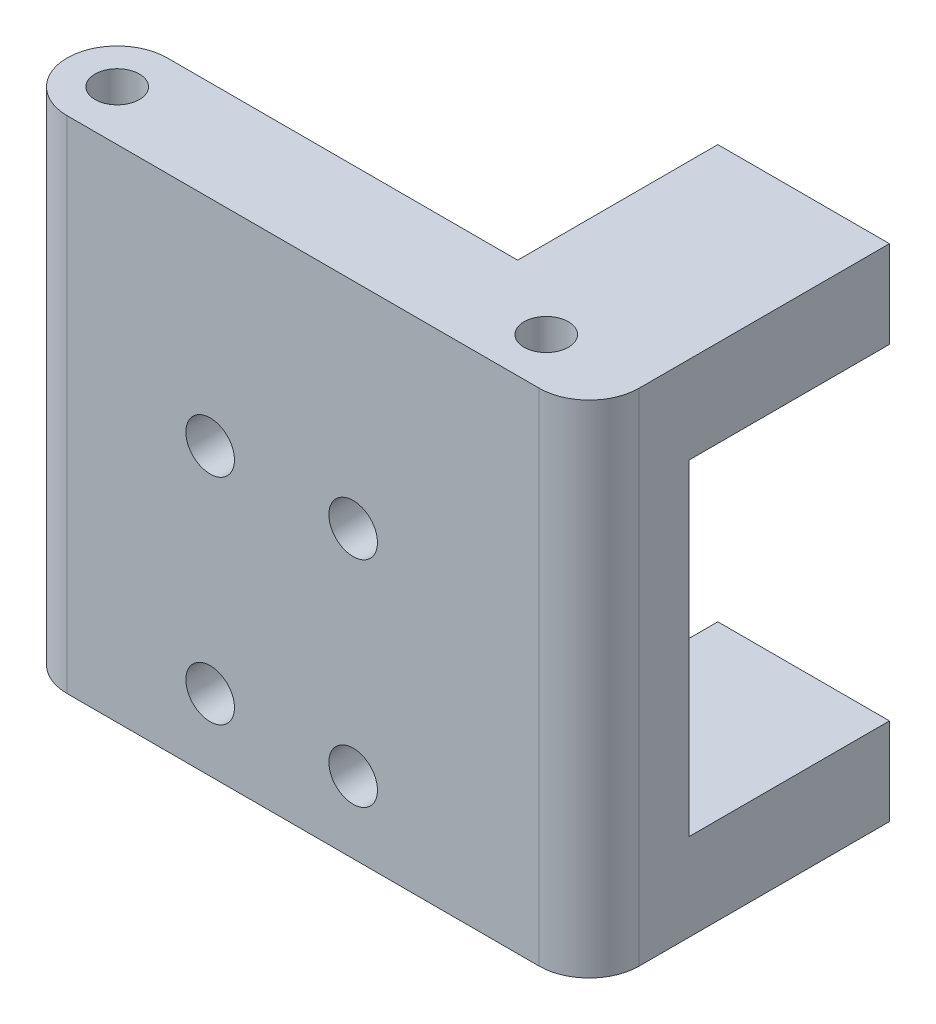
SolidWorks part; units mm, degrees
ref_plane "Ebene vorne" through (0, 0, 0) normal (0, 0, 1) x (1, 0, 0)
ref_plane "Ebene oben" through (0, 0, 0) normal (0, 1, 0) x (1, 0, 0)
ref_plane "Ebene rechts" through (0, 0, 0) normal (1, 0, 0) x (0, 0, -1)
sketch "Skizze1" plane through (0, 0, 0) normal (0, 1, 0) x (1, 0, 0)
  line L0 (-18.5, 0) -> (21.5, 0) construction
  line L1 (-18.5, 3.5) -> (21.5, 3.5)
  line L2 (-18.5, 3.5) -> (-18.5, -3.5)
  line L3 (-18.5, -3.5) -> (21.5, -3.5)
  line L4 (21.5, 3.5) -> (21.5, -3.5)
  circle A0 centre (-15, 0) radius 1.55
  circle A1 centre (15, 0) radius 1.55
  circle A2 centre (0, 0) radius 2.4
  point P4 (-18.5, 0)
  dimension "D3" = 3.1
  dimension "D4" = 3.1
  dimension "D8" = 4.8
  dimension "D1" = 30
  dimension "D2" = 7
  dimension "D5" = 15
  dimension "D6" = 3.5
  dimension "D7" = 6.5
extrude "Aufsatz-Linear austragen1" add sketch "Skizze1" along normal blind 35 contours L2 L1 L4 L3
sketch "Skizze2" plane through (0, 0, -3.5) normal (0, 0, -1) x (-1, 0, 0)
  line L0 (-21.5, 0) -> (18.5, 0) construction
  line L1 (-5, 20) -> (5, 20) construction
  line L2 (-5, 20) -> (-5, 5) construction
  line L3 (-5, 5) -> (5, 5) construction
  line L4 (5, 20) -> (5, 5) construction
  line L5 (-21.5, 0) -> (18.5, 0) construction
  line L6 (-21.5, 35) -> (-9.5, 35)
  line L7 (-21.5, 35) -> (-21.5, 0)
  line L8 (-21.5, 0) -> (-9.5, 0)
  line L9 (-9.5, 35) -> (-9.5, 0)
  line L10 (-21.5, 35) -> (-21.5, 0) construction
  line L11 (-21.5, 28.9) -> (-9.5, 28.9)
  line L12 (-21.5, 28.9) -> (-21.5, 6.1)
  line L13 (-21.5, 6.1) -> (-9.5, 6.1)
  line L14 (-9.5, 28.9) -> (-9.5, 6.1)
  line L15 (-15.5, 31.75) -> (-15.5, 3.25) construction
  circle A4 centre (-15.5, 31.75) radius 0.6
  circle A5 centre (-15.5, 3.25) radius 0.6
  point P4 (0, 5)
  point P6 (-5, 12.5)
  point P10 (-5, 20)
  point P11 (5, 20)
  point P12 (5, 5)
  point P24 (-21.5, 17.5)
  point P25 (-21.5, 17.5)
  point P26 (-5, 5)
  point P32 (-15.5, 17.5)
  point P33 (-9.5, 17.5)
  point P35 (-15.5, 35)
  line M5 (-21.5, 0) -> (18.5, 0)
  line M7 (18.5, 35) -> (-21.5, 35)
  line M17 (-21.5, 35) -> (-21.5, 0)
  dimension "D4" = 1.2
  dimension "D5" = 1.2
  dimension "D6" = 28.5
  dimension "D1" = 10
  dimension "D2" = 15
  dimension "D3" = 12.5
  dimension "D8" = 12
  dimension "D9" = 22.8
extrude "Aufsatz-Linear austragen2" add sketch "Skizze2" along normal blind 14 contours L11 L9 M17 M7 | L13 L9 M17 M5 region at (15.5, 34.8654, -3.5) region at (15.5, 5.9654, -3.5)
hole_wizard "Formsenkung für M3 Senkschraube mit Schlitz/Kreuzschlitz1" positions "Skizze6" profile "Skizze8" countersink size "M3" standard "ANSI Metric" end condition through all
sketch "Skizze6" plane through (0, 0, -3.5) normal (0, 0, -1) x (-1, 0, 0)
  point P0 (-5, 20)
  point P3 (5, 20)
  point P6 (5, 5)
  point P9 (-5, 5)
sketch "Skizze8" plane through (5, 20, -3.5) normal (1, 0, 0) x (0, 1, 0)
  line L0 (0, 0) -> (0, 7)
  line L1 (0, 7) -> (1.7, 7)
  line L2 (1.7, 7) -> (1.7, 1.45)
  line L3 (1.7, 1.45) -> (3.15, 0)
  line L5 (3.15, 0) -> (0, 0)
  line L6 (-1.7, 1.45) -> (-3.15, 0) construction
  line L11 (0, -6.35) -> (0, 107.95) construction
  dimension "Bohrerdurchmesser" = 3.4
  dimension "Bohrungstiefe" = 7
  dimension "Senkdurchmesser (Oben)" = 6.3
  dimension "Senkwinkel (Oben)" = 90
fillet "Verrundung1" radius 3.5 3 edges at (21.5, 17.5, 3.5) (-18.5, 17.5, 3.5) (-18.5, 17.5, -3.5)
extrude "Schnitt-Linear austragen1" cut sketch "Skizze1<5>" along normal through all contours A1 L0 | L0 A1 | A0 L0 | L0 A0 region at (15, 0, 0.6578) region at (15, 0, -0.6578) region at (-15, 0, 0.6578) region at (-15, 0, -0.6578)
sketch "Skizze1<5>" plane through (0, 0, 0) normal (0, 1, 0) x (1, 0, 0) same geometry as "Skizze1"
extrude "Schnitt-Linear austragen2" cut sketch "Skizze1<7>" along normal blind 2 contours A2 L0 | L0 A2 region at (0, 0, 1.0186) region at (0, 0, -1.0186)
sketch "Skizze1<7>" plane through (0, 0, 0) normal (0, 1, 0) x (1, 0, 0) same geometry as "Skizze1"
